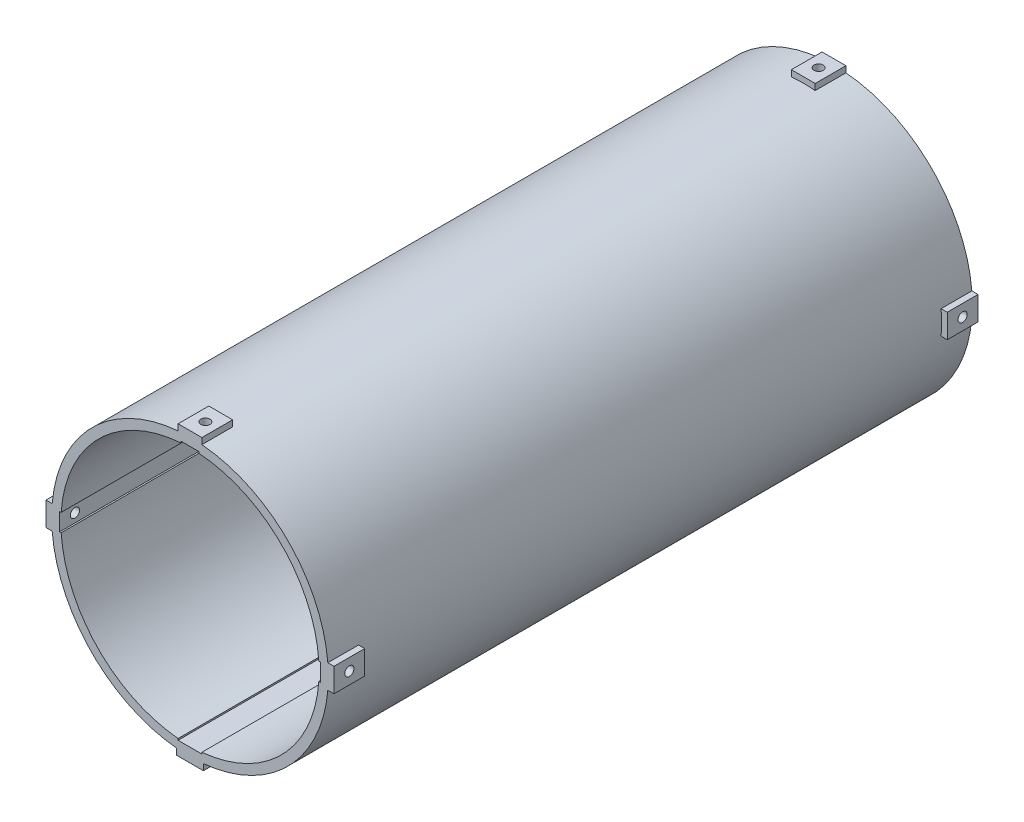
SolidWorks part; units mm, degrees
material "尼龙 101"
ref_plane "前视基准面" through (0, 0, 0) normal (0, 0, 1) x (1, 0, 0)
ref_plane "上视基准面" through (0, 0, 0) normal (0, 1, 0) x (1, 0, 0)
ref_plane "右视基准面" through (0, 0, 0) normal (1, 0, 0) x (0, 0, -1)
other "Configuration Table"
sketch "草图1" plane through (0, 0, 0) normal (0, 0, 1) x (1, 0, 0)
  line L2 (-8.75, -89.5736) -> (-8.75, -93.5875)
  line L3 (-8.75, -93.5875) -> (8.75, -93.5875)
  line L4 (8.75, -89.5736) -> (8.75, -93.5875)
  line L6 (7.75, 89.6657) -> (7.75, 93.6765)
  line L7 (7.75, 93.6765) -> (-7.75, 93.6765)
  line L8 (-7.75, 89.6657) -> (-7.75, 93.6765)
  line L9 (89.6657, 7.75) -> (93.6765, 7.75)
  line L11 (89.6657, -7.75) -> (93.6765, -7.75)
  line L12 (93.6765, 7.75) -> (93.6765, -7.75)
  line L13 (-89.6657, 7.75) -> (-93.6765, 7.75)
  line L15 (-89.6657, -7.75) -> (-93.6765, -7.75)
  line L16 (-93.6765, 7.75) -> (-93.6765, -7.75)
  circle A0 centre (0, 0) radius 93 construction
  arc A1 (8.75, -89.5736) -> (89.6657, -7.75) centre (0, 0) ccw
  arc A2 (-89.6657, -7.75) -> (-8.75, -89.5736) centre (0, 0) ccw
  arc A3 (89.6657, 7.75) -> (7.75, 89.6657) centre (0, 0) ccw
  arc A4 (-7.75, 89.6657) -> (-89.6657, 7.75) centre (0, 0) ccw
  point P8 (8.75, -92.5875)
  point P21 (7.75, 92.6765)
  point P22 (-92.6765, -7.75)
  point P25 (92.6765, -7.75)
  dimension "D1" = 186
  dimension "D2" = 180
  dimension "D3" = 17.5
  dimension "D4" = 1
  dimension "D5" = 15.5
  dimension "D6" = 1
  dimension "D7" = 15.5
  dimension "D8" = 15.5
  dimension "D9" = 1
  dimension "D10" = 1
extrude "凸台-拉伸1" add sketch "草图1" along normal blind 419
sketch "草图2" plane through (0, 0, 419) normal (0, 0, 1) x (1, 0, 0)
  circle A0 centre (0, 0) radius 90
  arc A1 (-7.75, 89.6657) -> (-89.6657, 7.75) centre (0, 0) ccw construction
  circle A2 centre (0, 0) radius 110
  dimension "D1" = 20
extrude "切除-拉伸1" cut sketch "草图2" against normal offset from surface (379 mm away) 20 from offset 20 up to face at (0, 0.0614, 0) offset against normal yes
sketch "草图3" plane through (0, 0, 419) normal (0, 0, 1) x (1, 0, 0)
  circle A0 centre (0, 0) radius 84
  arc A1 (-7.75, 89.6657) -> (-89.6657, 7.75) centre (0, 0) ccw construction
  dimension "D1" = 6
extrude "切除-拉伸2" cut sketch "草图3" against normal through all
sketch "草图4" plane through (0, 0, 419) normal (0, 0, 1) x (1, 0, 0)
  line L1 (-7.75, -83.6417) -> (7.75, -83.6417)
  line L2 (-7.75, -83.6417) -> (-7.75, -84.6417)
  line L3 (-7.75, -84.6417) -> (7.75, -84.6417)
  line L4 (7.75, -83.6417) -> (7.75, -84.6417)
  line L5 (-8.75, -89.5736) -> (-8.75, -93.5875) construction
  line L6 (-89.6657, 7.75) -> (-93.6765, 7.75) construction
  line L7 (-83.803, 5.75) -> (-84.803, 5.75)
  line L8 (-83.803, 5.75) -> (-83.803, -5.75)
  line L9 (-83.803, -5.75) -> (-84.803, -5.75)
  line L10 (-84.803, 5.75) -> (-84.803, -5.75)
  line L11 (7.75, 89.6657) -> (7.75, 93.6765) construction
  line L12 (-5.75, 83.803) -> (5.75, 83.803)
  line L13 (-5.75, 83.803) -> (-5.75, 84.803)
  line L14 (-5.75, 84.803) -> (5.75, 84.803)
  line L15 (5.75, 83.803) -> (5.75, 84.803)
  line L16 (93.6765, 7.75) -> (89.6657, 7.75) construction
  line L17 (83.803, 5.75) -> (84.803, 5.75)
  line L18 (83.803, 5.75) -> (83.803, -5.75)
  line L19 (83.803, -5.75) -> (84.803, -5.75)
  line L20 (84.803, 5.75) -> (84.803, -5.75)
  circle A0 centre (0, 0) radius 84 construction
  dimension "D1" = 1
  dimension "D2" = 1
  dimension "D3" = 2
  dimension "D4" = 1
  dimension "D5" = 1
  dimension "D6" = 2
  dimension "D7" = 2
  dimension "D8" = 1
extrude "切除-拉伸3" cut sketch "草图4" against normal through all
sketch "草图5" plane through (-84.803, 0, 0) normal (1, 0, 0) x (0, 0, -1)
  line L0 (-419, 5.75) -> (-419, -5.75) construction
  line L1 (0, 5.75) -> (0, -5.75) construction
  circle A0 centre (-409, 0) radius 3
  circle A1 centre (-10, 0) radius 3
  point P4 (-419, 0)
  point P10 (0, 0)
  dimension "D2" = 6
  dimension "D4" = 6
  dimension "D1" = 10
  dimension "D3" = 10
extrude "切除-拉伸4" cut sketch "草图5" against normal through all
sketch "草图6" plane through (0, 0, 0) normal (0, 1, 0) x (1, 0, 0)
  line L0 (0, -1000) -> (0, 49000) construction
pattern_circular "阵列(圆周)1" count 4 every 90 about axis through (0, 0, 1000) along (0, 0, -1) of "切除-拉伸4"
